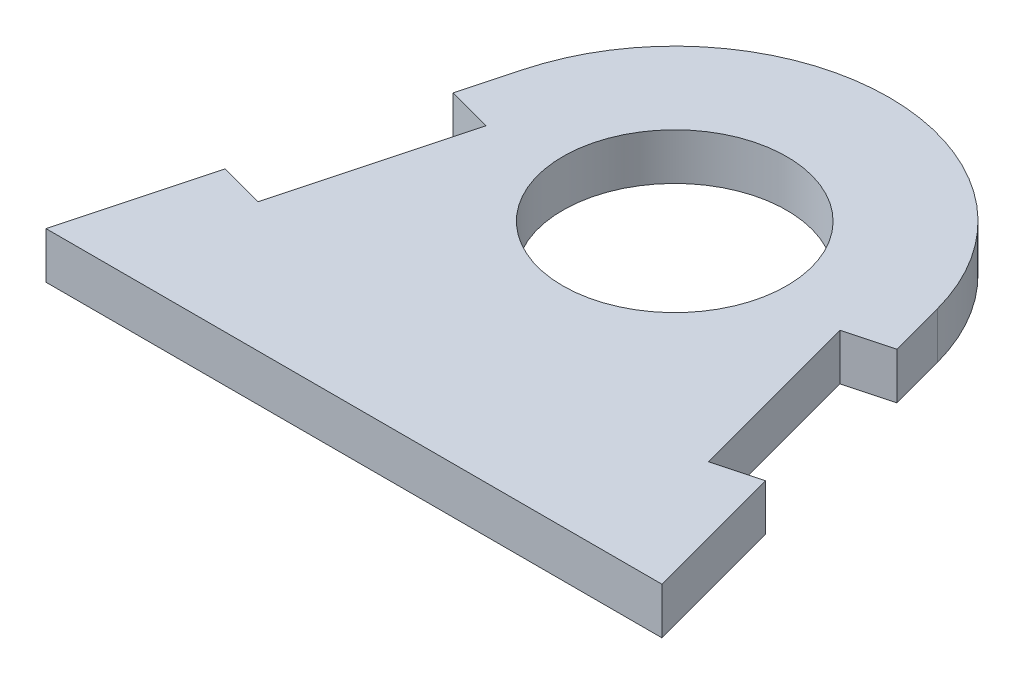
SolidWorks part; units mm, degrees
ref_plane "Front Plane" through (0, 0, 0) normal (0, 0, 1) x (1, 0, 0)
ref_plane "Top Plane" through (0, 0, 0) normal (0, 1, 0) x (1, 0, 0)
ref_plane "Right Plane" through (0, 0, 0) normal (1, 0, 0) x (0, 0, -1)
sketch "Sketch1" plane through (0, 0, 0) normal (0, 1, 0) x (1, 0, 0)
  line L0 (-21.0382, 0) -> (21.0382, 0)
  line L1 (21.0382, 0) -> (14.1508, 25.7042)
  line L2 (-21.0382, 0) -> (-14.1508, 25.7042)
  line L3 (15.163, 21.9265) -> (18.45, 9.6593)
  line L4 (15.163, 21.9265) -> (12.0962, 21.1048)
  line L5 (18.45, 9.6593) -> (15.3832, 8.8375)
  line L6 (12.0962, 21.1048) -> (15.3832, 8.8375)
  line L7 (-15.163, 21.9265) -> (-18.45, 9.6593)
  line L8 (-15.163, 21.9265) -> (-12.0962, 21.1048)
  line L9 (-18.45, 9.6593) -> (-15.3832, 8.8375)
  line L10 (-12.0962, 21.1048) -> (-15.3832, 8.8375)
  circle A0 centre (0, 21.9125) radius 7.65
  arc A1 (-14.1508, 25.7042) -> (14.1508, 25.7042) centre (0, 21.9125) cw
  point P10 (0, 0)
  point P11 (0, 21.9125)
  dimension "D2" = 15.3
  dimension "D3" = 7
  dimension "D1" = 21.9125
  dimension "D4" = 75
  dimension "D5" = 3.175
  dimension "D6" = 12.7
  dimension "D7" = 10
  dimension "D8" = 10
extrude "Boss-Extrude1" add sketch "Sketch1" along normal mid plane 3.175 contours A1 L2 L8 L10 L9 L0 L1 L5 L6 L4 A0 region at (-19.2057, 0, -4.6854)
ref_axis "Axis1" through (0, 0, -21.9125) along (0, 1, 0)
